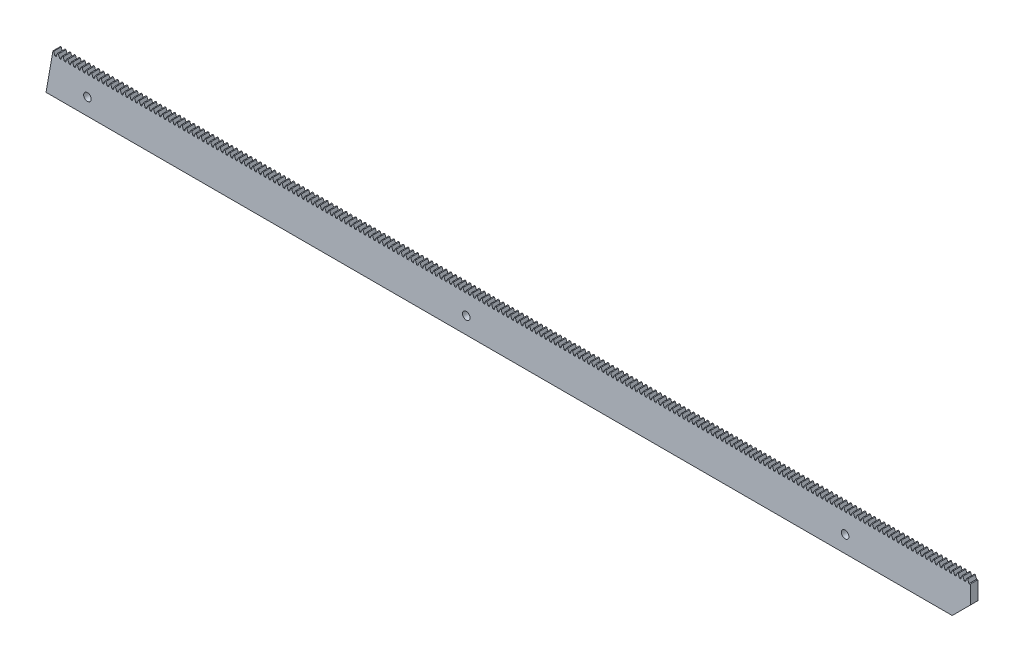
SolidWorks part; units mm, degrees
extrude "Blank" add sketch "BlankSke" against normal blind 10
sketch "BlankSke" plane through (0, 0, 0) normal (0, 0, 1) x (1, 0, 0)
  line L1 (0, 0) -> (1220, 0)
  line L2 (0, 0) -> (0, 52)
  line L3 (0, 52) -> (1220, 52)
  line L4 (1220, 0) -> (1220, 52)
  dimension "Length" = 1220
ref_plane "Plane1" through (0, 0, 0) normal (0, 0, 1) x (1, 0, 0)
ref_plane "Plane2" through (0, 0, 0) normal (0, 1, 0) x (1, 0, 0)
ref_plane "Plane3" through (0, 0, 0) normal (1, 0, 0) x (0, 0, -1)
sketch "HoldingSke" plane through (0, 0, 0) normal (0, 1, 0) x (1, 0, 0)
  line L0 (0, 0) -> (0.0696, 0.4951)
  line L1 (-15, 0) -> (100, 0) construction
  line L2 (0, 0) -> (-2.1039, 2.3779)
  line L3 (0, 0) -> (-11.863, 4.5341)
  line L4 (0, 0) -> (-8.3015, -2.3804)
  line L5 (0, 0) -> (-23.7986, -8.8762)
  line L6 (0, 0) -> (-10.5278, -7.1032)
  line L9 (-71.009, 38.7566) -> (1075.416, 456.0212)
  line L10 (-76.2, 4.3779) -> (-26.2, 4.3779)
  line L11 (0, 0) -> (-10, 0)
  line L12 (-76.2, 101.6) -> (-76.133, 101.6)
  line L13 (24.9733, 27.94) -> (52.9518, 28.4284)
  line L14 (24.9733, 27.94) -> (24.9743, 27.94)
  line L15 (24.9733, 27.94) -> (100.4006, 29.5858)
  circle A0 centre (0, 0) radius 19.05
  circle A1 centre (0, 0) radius 25
  circle A2 centre (0, 0) radius 12.7
  dimension "Num_teeth" = 196
  dimension "Width" = 10
  dimension "Length" = 1220
  dimension "Pitch_height" = 50
sketch "TooCutSkeIll" plane through (0, 0, 0) normal (0, 0, 1) x (1, 0, 0)
  line L0 (-2.4806, 51.9474) -> (-0.9819, 47.8296)
  line L1 (-0.5111, 47.5) -> (0.5111, 47.5)
  line L2 (0.9819, 47.8296) -> (2.4806, 51.9474)
  line L3 (1220, 52) -> (0, 52) construction
  line L4 (0, 0) -> (0, 64.897) construction
  line L5 (-13.208, 50) -> (12.954, 50) construction
  line L6 (0, 0) -> (1220, 0) construction
  line L7 (1.7718, 50) -> (1.7718, 48.7463) construction
  line L8 (-1.7718, 50) -> (-1.7718, 48.7463) construction
  line L9 (2.5558, 52) -> (2.5558, 52.0254)
  line L10 (-2.5558, 52) -> (-2.5558, 52.0254)
  line L11 (-2.5558, 52.0254) -> (2.5558, 52.0254)
  arc A0 (0.5111, 47.5) -> (0.9819, 47.8296) centre (0.5111, 48.001) ccw
  arc A1 (-0.9819, 47.8296) -> (-0.5111, 47.5) centre (-0.5111, 48.001) ccw
  arc A2 (2.5558, 52) -> (2.4806, 51.9474) centre (2.5558, 51.92) ccw
  arc A3 (-2.4806, 51.9474) -> (-2.5558, 52) centre (-2.5558, 51.92) ccw
  dimension "Addendum_plus" = 2.0254
  dimension "Pitch_height" = 50
  dimension "Pressure_angle" = 20
  dimension "Gap_width" = 3.5436
  dimension "Dedendum" = 2.5
extrude "ToothCutIll" [suppressed] cut sketch "TooCutSkeIll" against normal through all
sketch "TooCutSkeSim" plane through (0, 0, 0) normal (0, 0, 1) x (1, 0, 0)
  line L0 (0.8619, 47.5) -> (-0.8619, 47.5)
  line L1 (2.509, 52.0254) -> (0.8619, 47.5)
  line L2 (0, 17.4625) -> (0, 53.467) construction
  line L3 (2.509, 52.0254) -> (-2.509, 52.0254)
  line L6 (-2.509, 52.0254) -> (-0.8619, 47.5)
  line L9 (-1.7718, 50) -> (1.7718, 50) construction
  line L10 (0, 0) -> (1220, 0) construction
  line L11 (1.7718, 50) -> (1.7718, 53.467) construction
  line L12 (-1.7718, 50) -> (-1.7718, 53.467) construction
  dimension "Addendum_plus" = 2.0254
  dimension "Pitch_height" = 50
  dimension "Pressure_angle" = 20
  dimension "Gap_width" = 3.5436
  dimension "Dedendum" = 2.5
extrude "ToothCutSim" cut sketch "TooCutSkeSim" against normal through all
pattern_linear "TeethCuts" count 196 spacing 6.2832 along (1, 0, 0) of "ToothCutIll", "ToothCutSim"
sketch "Эскиз1" plane through (0, 0, 0) normal (0, 0, 1) x (1, 0, 0)
  line L0 (0, 0) -> (11.6729, 66.2003)
  line L1 (11.6729, 66.2003) -> (0, 64.6577)
  line L2 (0, 64.6577) -> (0, 0)
  dimension "D1" = 10
  dimension "D2" = 64.6577
  dimension "D3" = 11.6729
extrude "Вырез-Вытянуть1" cut sketch "Эскиз1" against normal through all
sketch "Эскиз2" plane through (0, 0, 0) normal (0, 0, 1) x (1, 0, 0)
  line L0 (47.7657, 52) -> (46.482, 52) construction
  line L1 (0, 0) -> (9.169, 52) construction
  line L2 (569.2701, 52) -> (567.9864, 52) construction
  line L3 (1059.3586, 52) -> (1058.0749, 52) construction
  circle A0 centre (54.6505, 22) radius 5
  circle A1 centre (554.6505, 22) radius 5
  circle A2 centre (1054.6505, 22) radius 5
  dimension "D1" = 10
  dimension "D5" = 10
  dimension "D8" = 10
  dimension "D2" = 30
  dimension "D3" = 50
  dimension "D4" = 500
  dimension "D6" = 30
  dimension "D7" = 500
  dimension "D9" = 30
extrude "Вырез-Вытянуть2" cut sketch "Эскиз2" against normal through all
sketch "Эскиз3" plane through (0, 0, 0) normal (0, 0, 1) x (1, 0, 0)
  line L0 (1220, 24.025) -> (1195.975, 0)
  line L1 (1220, 0) -> (1220, 48.05) construction
  line L2 (0, 0) -> (1220, 0) construction
  line L3 (1195.975, 0) -> (1236.0439, 0)
  line L4 (1236.0439, 0) -> (1220, 24.025)
  dimension "D1" = 45
  dimension "D2" = 28.8896
extrude "Вырез-Вытянуть3" cut sketch "Эскиз3" against normal through all
equation "' \"Module@HoldingSke\" = 6.35"
equation "' \"Num_teeth@HoldingSke\" = 12"
equation "' \"Ap@HoldingSke\" =  20"
equation "' \"Ap@HoldingSke\" = 20"
equation "' \"Width@HoldingSke\" = 0.25 * 25.4"
equation "' \"Show_teeth@HoldingSke\" = 500"
equation "' \"Backlash@HoldingSke\" = 0.009 * 25.4"
equation "' \"Addendum_fac@HoldingSke\" = 1.0"
equation "' \"Dedendum_fac@HoldingSke\" = 1.25"
equation "' \"Dedendum_add@HoldingSke\" = 0.00005 * 25.4"
equation "' \"Clearance_fac@HoldingSke\" = 0.25"
equation "' \"Pitch_height@HoldingSke\" = 1 * 25.4"
equation "' \"Length@HoldingSke\" = 4.71 * 25.4"
equation "\"Pitch@HoldingSke\" = 1 / \"Module@HoldingSke\""
equation "\"MPH@HoldingSke\" = \"Dedendum_fac@HoldingSke\" / \"Pitch@HoldingSke\" + 2 * \"Dedendum_add@HoldingSke\" + 0.002 * 25.4"
equation "\"MPH@HoldingSke\" = ((sgn( \"MPH@HoldingSke\" - \"Pitch_height@HoldingSke\")+1)*( \"MPH@HoldingSke\" - \"Pitch_height@HoldingSke\"))/2 + \"Pitch_height@HoldingSke\""
equation "\"Blank_height@BlankSke\" = \"Pitch_height@HoldingSke\" + \"Addendum_fac@HoldingSke\"  / \"Pitch@HoldingSke\" "
equation "\"Length@BlankSke\" =  \"Length@HoldingSke\""
equation "\"Face_width@Blank\" = \"Width@HoldingSke\""
equation "\"Pressure_angle@TooCutSkeIll\" = \"Ap@HoldingSke\""
equation "\"Addendum_plus@TooCutSkeIll\" =  \"Addendum_fac@HoldingSke\"  / \"Pitch@HoldingSke\" + 0.001 *25.4"
equation "\"Dedendum@TooCutSkeIll\" = \"Dedendum_fac@HoldingSke\"  / \"Pitch@HoldingSke\""
equation "\"Pitch_height@TooCutSkeIll\" =  \"MPH@HoldingSke\""
equation "\"Gap_width@TooCutSkeIll\" = 3.14159265 / 2 / \"Pitch@HoldingSke\" + 6 * \"Backlash@HoldingSke\""
equation "\"Pressure_angle@TooCutSkeSim\" = \"Ap@HoldingSke\""
equation "\"Addendum_plus@TooCutSkeSim\" =  \"Addendum_fac@HoldingSke\"  / \"Pitch@HoldingSke\" + 0.001 * 25.4"
equation "\"Dedendum@TooCutSkeSim\" = \"Dedendum_fac@HoldingSke\"  / \"Pitch@HoldingSke\""
equation "\"Pitch_height@TooCutSkeSim\" =  \"MPH@HoldingSke\""
equation "\"Gap_width@TooCutSkeSim\" = 3.14159265 / 2 / \"Pitch@HoldingSke\" + 6 * \"Backlash@HoldingSke\""
equation "\"Root_fillet@TooCutSkeIll\" = \"Clearance_fac@HoldingSke\" / \"Pitch@HoldingSke\" + \"Dedendum_add@HoldingSke\""
equation "\"Break_rad@TooCutSkeIll\" = 0.02 / \"Pitch@HoldingSke\" * 2"
equation "\"Linear_pitch@TeethCuts\" = 3.14159265 / \"Pitch@HoldingSke\""
equation "\"Num_teeth@HoldingSke\" = int( ( \"Length@HoldingSke\" + 0 ) / (3.14159265 / \"Pitch@HoldingSke\")) + 0.9999  + 1"
equation " \"Num_teeth@TeethCuts\" = int( \"Show_teeth@HoldingSke\" ) + 1"
equation " \"Num_teeth@TeethCuts\" = ((sgn( \"Num_teeth@TeethCuts\" - \"Num_teeth@HoldingSke\" )-1)*( \"Num_teeth@TeethCuts\" - \"Num_teeth@HoldingSke\" ))/-2+ \"Num_teeth@HoldingSke\""
equation " \"Num_teeth@TeethCuts\" = ((sgn( \"Num_teeth@TeethCuts\" - 2.0)+1)*( \"Num_teeth@TeethCuts\" - 2.0))/2 +2.0"
